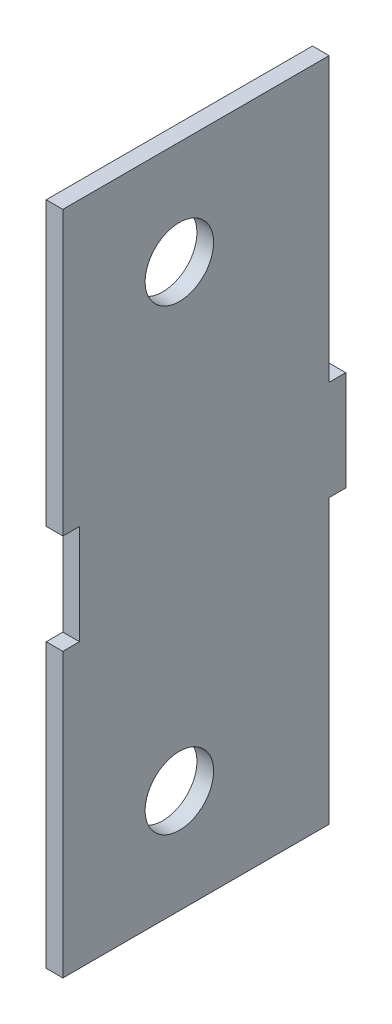
SolidWorks part; units mm, degrees
material "AISI 4130 Steel, annealed at 865C"
ref_plane "Front Plane" through (0, 0, 0) normal (0, 0, 1) x (1, 0, 0)
ref_plane "Top Plane" through (0, 0, 0) normal (0, 1, 0) x (1, 0, 0)
ref_plane "Right Plane" through (0, 0, 0) normal (1, 0, 0) x (0, 0, -1)
sketch "Sketch2" plane through (0, 0, 0) normal (1, 0, 0) x (0, 0, -1)
  line L0 (-1.5875, 21.844) -> (-1.5875, -21.844) construction
  line L1 (-12.7, -31.75) -> (12.7, -31.75)
  line L2 (-12.7, -31.75) -> (-12.7, 31.75)
  line L3 (-12.7, 31.75) -> (12.7, 31.75)
  line L4 (12.7, -31.75) -> (12.7, 31.75)
  line L5 (-12.7, -31.75) -> (12.7, 31.75) construction
  line L6 (-12.7, 31.75) -> (12.7, -31.75) construction
  line L7 (0, 0) -> (-1.5875, 0) construction
  circle A0 centre (-1.5875, 21.844) radius 3.2639
  circle A1 centre (-1.5875, -21.844) radius 3.2639
  point P0 (0, 0)
  point P6 (0, 0)
  point P13 (-1.5875, 0)
  point P14 (-4.7698, 0)
  dimension "D3" = 6.5278
  dimension "D4" = 6.5278
  dimension "D1" = 25.4
  dimension "D2" = 63.5
  dimension "D5" = 90
  dimension "D6" = 43.688
  dimension "D7" = 1.5875
extrude "Boss-Extrude1" add sketch "Sketch2" along normal blind 1.5875
sketch "Sketch3" plane through (1.5875, 0, 0) normal (1, 0, 0) x (0, 0, -1)
  line L0 (-12.7, 0) -> (12.7, 0) construction
  line L1 (-12.7, 31.75) -> (-12.7, -31.75) construction
  line L2 (12.7, -31.75) -> (12.7, 31.75) construction
  line L4 (-12.7, 4.7625) -> (-11.1125, 4.7625)
  line L5 (-12.7, 4.7625) -> (-12.7, -4.7625)
  line L6 (-12.7, -4.7625) -> (-11.1125, -4.7625)
  line L7 (-11.1125, 4.7625) -> (-11.1125, -4.7625)
  line L8 (12.7, 4.7625) -> (14.2875, 4.7625)
  line L9 (12.7, 4.7625) -> (12.7, -4.7625)
  line L10 (12.7, -4.7625) -> (14.2875, -4.7625)
  line L11 (14.2875, 4.7625) -> (14.2875, -4.7625)
  point P14 (-11.1125, 0)
  dimension "D1" = 9.525
  dimension "D2" = 1.5875
  dimension "D3" = 1.5875
extrude "Boss-Extrude2" add sketch "Sketch3" against normal blind 1.5875 contours L9 L8 L11 L10
extrude "Cut-Extrude1" cut sketch "Sketch3<4>" against normal blind 3.175 contours L7 L6 L5 L4
sketch "Sketch3<4>" plane through (1.5875, 0, 0) normal (1, 0, 0) x (0, 0, -1) same geometry as "Sketch3"
